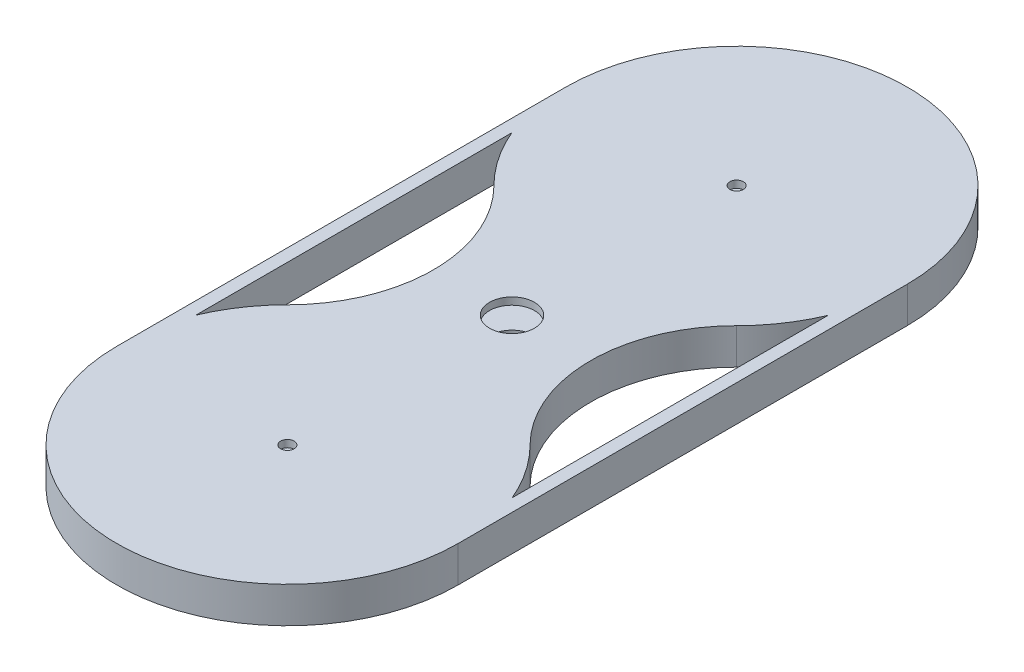
SolidWorks part; units mm, degrees
ref_plane "Front Plane" through (0, 0, 0) normal (0, 0, 1) x (1, 0, 0)
ref_plane "Top Plane" through (0, 0, 0) normal (0, 1, 0) x (1, 0, 0)
ref_plane "Right Plane" through (0, 0, 0) normal (1, 0, 0) x (0, 0, -1)
sketch "Sketch1" plane through (0, 0, 0) normal (0, 1, 0) x (1, 0, 0)
  line L1 (-19, 0) -> (-19, -50)
  line L2 (19, 0) -> (19, -50)
  arc A0 (19, 0) -> (-19, 0) centre (0, 0) ccw
  arc A1 (-19, -50) -> (19, -50) centre (0, -50) ccw
  dimension "D1" = 38
extrude "Boss-Extrude1" add sketch "Sketch1" along normal blind 2 and the other way blind 2
sketch "Sketch3" plane through (0, 0, 0) normal (0, 1, 0) x (1, 0, 0)
  arc A0 (12.4451, -12.4451) -> (-12.4451, -12.4451) centre (0, 0) ccw
  arc A1 (-12.4451, -37.5549) -> (12.4451, -37.5549) centre (0, -50) ccw
  arc A2 (-12.4451, -37.5549) -> (-17.6, -50) centre (0, -50) ccw
  arc A3 (-12.4451, -12.4451) -> (-17.6, 0) centre (0, 0) cw
  arc A4 (-12.4451, -12.4451) -> (-12.4451, -37.5549) centre (-25, -25) cw
  arc A5 (12.4451, -37.5549) -> (17.6, -50) centre (0, -50) cw
  arc A6 (12.4451, -12.4451) -> (17.6, 0) centre (0, 0) ccw
  arc A7 (12.4451, -12.4451) -> (12.4451, -37.5549) centre (25, -25) ccw
extrude "Cut-Extrude1" cut sketch "Sketch3" against normal blind 1.2 and the other way blind 1.2 contours A7 A0 A4 A1 region at (0, 0, 25)
sketch "Sketch4" plane through (0, -2, 0) normal (0, -1, 0) x (1, 0, 0)
  line L0 (19, 25) -> (-19, 25) construction
  line L1 (19, 50) -> (19, 0) construction
  line L2 (-19, 0) -> (-19, 50) construction
  line L4 (-17, 19.5) -> (-10, 19.5)
  line L5 (-17, 19.5) -> (-17, 30.5)
  line L6 (-17, 30.5) -> (-10, 30.5)
  line L7 (-10, 19.5) -> (-10, 30.5)
  line L8 (-17, 19.5) -> (-10, 30.5) construction
  line L9 (-17, 30.5) -> (-10, 19.5) construction
  line L10 (10, 19.5) -> (17, 19.5)
  line L11 (10, 19.5) -> (10, 30.5)
  line L12 (10, 30.5) -> (17, 30.5)
  line L13 (17, 19.5) -> (17, 30.5)
  line L14 (10, 19.5) -> (17, 30.5) construction
  line L15 (10, 30.5) -> (17, 19.5) construction
  point P6 (-13.5, 25)
  point P11 (13.5, 25)
  dimension "D1" = 11
  dimension "D2" = 7
  dimension "D3" = 7
  dimension "D4" = 2
  dimension "D5" = 2
extrude "Boss-Extrude2" add sketch "Sketch4" along normal blind 1.2
ref_plane "Plane1" through (13.5, 0, 0) normal (1, 0, 0) x (0, 0, -1)
ref_plane "Plane2" through (-13.5, 0, 0) normal (1, 0, 0) x (0, 0, -1)
sketch "Sketch6" plane through (-13.5, 0, 0) normal (1, 0, 0) x (0, 0, -1)
  line L0 (-19.5, -3.2) -> (-30.5, -3.2) construction
  line L1 (-22.3, -3.2) -> (-22.3, -5.3)
  arc A0 (-22.3, -5.3) -> (-26.972, -5.9077) centre (-24.6755, -5.3) cw
  dimension "D1" = 2.8
  dimension "D2" = 2.1
sweep "Sweep1" add path "Sketch6" circular profile diameter 2 parameters "D3"=2
mirror "Mirror1" about plane through (0, 0, 0) normal (1, 0, 0) of "Sweep1"
sketch "Sketch25" plane through (0, -2, 0) normal (0, -1, 0) x (1, 0, 0)
  circle A0 centre (0, 0) radius 2.2
  circle A1 centre (0, 50) radius 2.2
extrude "Cut-Extrude2" cut sketch "Sketch25" against normal blind 2.2
sketch "Sketch26" plane through (0, -2, 0) normal (0, -1, 0) x (-1, 0, 0)
  circle A0 centre (0, -25) radius 2.5
  circle A1 centre (0, -50) radius 0.75
  circle A2 centre (0, 0) radius 0.75
extrude "Cut-Extrude3" cut sketch "Sketch26" against normal blind 10.2
sketch "Sketch27" plane through (0, -2, 0) normal (0, -1, 0) x (1, 0, 0)
  line L0 (-17.6, 7.4196) -> (-17.6, 42.5804)
  line L1 (17.6, 42.5804) -> (17.6, 7.4196)
  line L2 (-8.7447, 25) -> (-8.74, 25) construction
  line L3 (8.7447, 25) -> (8.704, 25) construction
  arc A0 (17.6, 7.4196) -> (13.5057, 13.5057) centre (0, 0) ccw
  arc A1 (-17.6, 42.5804) -> (-13.5057, 36.4943) centre (0, 50) ccw
  arc A6 (13.5057, 36.4943) -> (-13.5057, 36.4943) centre (0, 50) ccw
  arc A7 (-13.5057, 13.5057) -> (-13.5057, 36.4943) centre (-25, 25) ccw
  arc A8 (13.5057, 36.4943) -> (17.6, 42.5804) centre (0, 50) ccw
  arc A9 (-13.5057, 13.5057) -> (-13.5057, 36.4943) centre (-25, 25) ccw
  arc A13 (13.5057, 36.4943) -> (13.5057, 13.5057) centre (25, 25) ccw
  arc A14 (-13.5057, 13.5057) -> (13.5057, 13.5057) centre (0, 0) ccw
  arc A15 (13.5057, 36.4943) -> (13.5057, 13.5057) centre (25, 25) ccw
  arc A16 (-13.5057, 13.5057) -> (-17.6, 7.4196) centre (0, 0) ccw
  point P3 (-17.6, 25)
  point P4 (-17.6, 25)
  point P6 (17.6, 25)
  point P8 (17.6, 25)
  dimension "D2" = 1.5
  dimension "D3" = 1.5
extrude "Cut-Extrude4" cut sketch "Sketch27" against normal blind 10 and the other way blind 10
